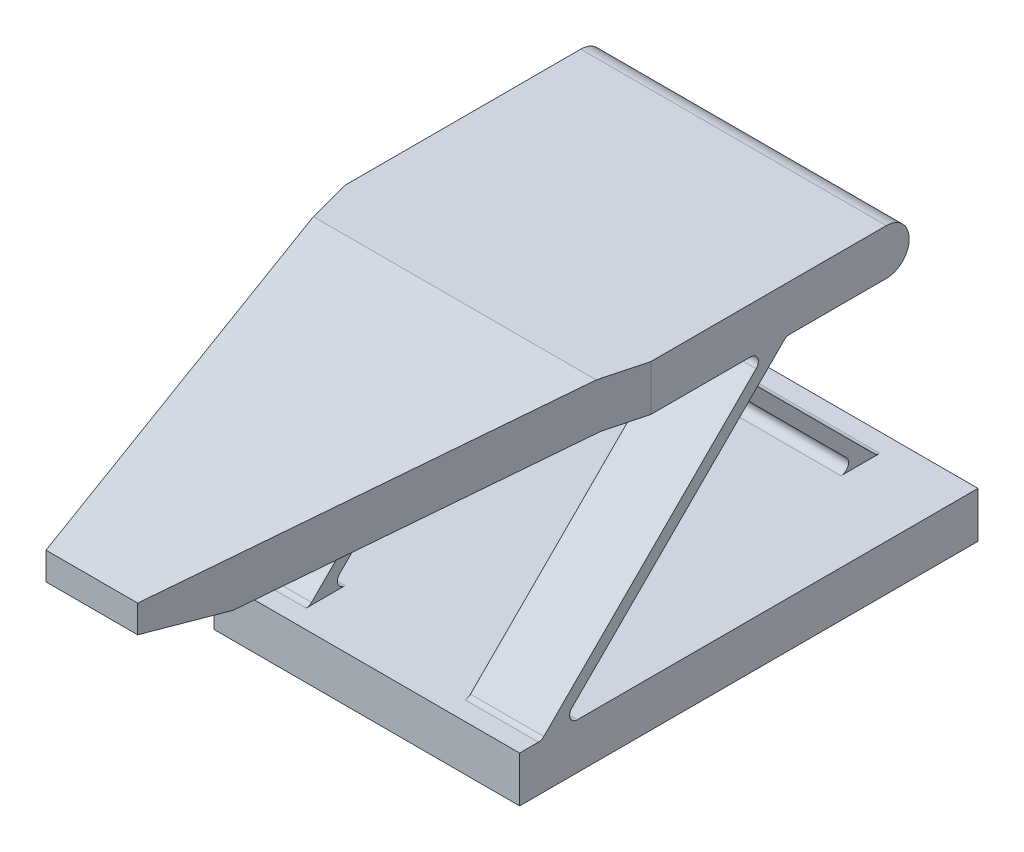
SolidWorks part; units mm, degrees
ref_plane "Front" through (0, 0, 0) normal (0, 0, 1) x (1, 0, 0)
ref_plane "Top" through (0, 0, 0) normal (0, 1, 0) x (1, 0, 0)
ref_plane "Right" through (0, 0, 0) normal (1, 0, 0) x (0, 0, -1)
ref_axis "X" through (-80.9, 0, 0) along (1, 0, 0)
ref_axis "Y" through (0, -50, 0) along (0, 1, 0)
ref_axis "Z" through (0, 0, -80.9) along (0, 0, 1)
sketch "Sketch1" plane through (0, 0, 0) normal (1, 0, 0) x (0, 0, -1)
  line L0 (0, 13) -> (0, 11.2)
  line L1 (0, 11.2) -> (4.9304, 10.7686)
  line L4 (0, 0) -> (0, -4) construction
  line L5 (0, -4) -> (30.1272, -4) construction
  line L6 (18, -4) -> (48, -4)
  line L7 (48, -4) -> (48, -1)
  line L9 (18, -1) -> (18, -4)
  line L11 (24, 13.8967) -> (42, 13.8967)
  line L13 (42, 16.8967) -> (23.7556, 16.8967)
  line L14 (33, 13.8967) -> (33, -1) construction
  line L15 (31.1033, 13.8967) -> (46, -1) construction
  line L16 (34.8967, 13.8967) -> (20, -1) construction
  line L17 (46, -1) -> (33, -1) construction
  line L18 (33, -1) -> (20, -1) construction
  line L19 (18, -1) -> (48, -1)
  line L20 (0, 13) -> (23.7556, 16.8967)
  line L21 (24, 13.8967) -> (4.9304, 10.7686)
  line L22 (24, 13.8967) -> (23.5144, 16.8571) construction
  line L24 (42, 16.8967) -> (42, 13.8967) construction
  circle A0 centre (0, 0) radius 13 construction
  circle A1 centre (0, 0) radius 1.5 construction
  arc A2 (42, 16.8967) -> (42, 13.8967) centre (42, 15.3967) cw
  point P24 (33, 12)
  point P29 (18, -2.5)
  dimension "D1" = 26
  dimension "D4" = 3
  dimension "D2" = 1.8
  dimension "D3" = 5
  dimension "D5" = 4
  dimension "D6" = 3
  dimension "D8" = 2
  dimension "D9" = 18.3848
  dimension "D7" = 21.0671
  dimension "D10" = 9
  dimension "D11" = 3
  dimension "D12" = 18
extrude "Boss-Extrude1" add sketch "Sketch1" along normal mid plane 20
sketch "Sketch2" plane through (0, 0, 0) normal (1, 0, 0) x (0, 0, -1)
  line L0 (31.1033, 13.8967) -> (46, -1) construction
  line L1 (30.5376, 13.8967) -> (45.4343, -1)
  line L2 (31.669, 13.8967) -> (46.5657, -1)
  line L3 (18, -1) -> (48, -1) construction
  line L4 (24, 13.8967) -> (42, 13.8967) construction
  line L5 (45.4343, -1) -> (46.5657, -1)
  line L6 (30.5376, 13.8967) -> (31.669, 13.8967)
  line L7 (31.3862, 14.1795) -> (46.2828, -0.7172) construction
  line L8 (30.8205, 13.6138) -> (45.7172, -1.2828) construction
  dimension "D1" = 0.4
  dimension "D2" = 0.4
extrude "Boss-Extrude2" add sketch "Sketch2" along normal mid plane 9.6
sketch "Sketch3" plane through (0, 0, 0) normal (1, 0, 0) x (0, 0, -1)
  line L0 (34.8967, 13.8967) -> (20, -1) construction
  line L1 (18, -1) -> (48, -1) construction
  line L2 (24, 13.8967) -> (42, 13.8967) construction
  line L3 (19.4343, -1) -> (20.5657, -1)
  line L4 (34.331, 13.8967) -> (35.4624, 13.8967)
  line L5 (34.331, 13.8967) -> (19.4343, -1)
  line L6 (35.4624, 13.8967) -> (20.5657, -1)
  line L7 (35.1795, 13.6138) -> (20.2828, -1.2828) construction
  line L8 (34.6138, 14.1795) -> (19.7172, -0.7172) construction
  dimension "D1" = 0.4
  dimension "D2" = 0.4
extrude "Boss-Extrude3" add sketch "Sketch3" along normal blind 4.8 from offset 5.2
mirror "Mirror1" about plane through (0, 0, 0) normal (1, 0, 0) of "Boss-Extrude3"
fillet "Fillet1" radius 0.5 10 edges at (-7.6, -1, -20.5657) (-7.6, -1, -19.4343) (7.6, -1, -19.4343) (7.6, -1, -20.5657) (0, -1, -45.4343) (0, -1, -46.5657) (0, 13.8967, -31.669) (0, 13.8967, -30.5376) (7.6, 13.8967, -34.331) (7.6, 13.8967, -35.4624)
sketch "Sketch4" plane through (0, 16.8967, 0) normal (0, 1, 0) x (1, 0, 0)
  line L0 (-3, 0) -> (-10, 26.5853)
  line L1 (10, 0) -> (-10, 0) construction
  line L2 (-10, 42) -> (-10, 23.7556) construction
  line L3 (-10, 26.5853) -> (-10, 0)
  line L4 (-10, 0) -> (-3, 0)
  line L5 (3, 0) -> (10, 0)
  line L6 (10, 0) -> (10, 26.5853)
  line L7 (10, 42) -> (10, 23.7556) construction
  line L8 (10, 26.5853) -> (3, 0)
  line L9 (0, 0) -> (0, 50.5606) construction
  point P17 (0, 0)
  point P18 (0, 0)
  point P19 (-10, 26.5853)
  point P20 (-2.2688, 0)
  dimension "D1" = 6
extrude "Cut-Extrude1" cut sketch "Sketch4" against normal up to next
equation "\"D7@Sketch1\"= \"D9@Sketch1\" / ( 0.5 + sqr ( 5 ) / 6 )"
